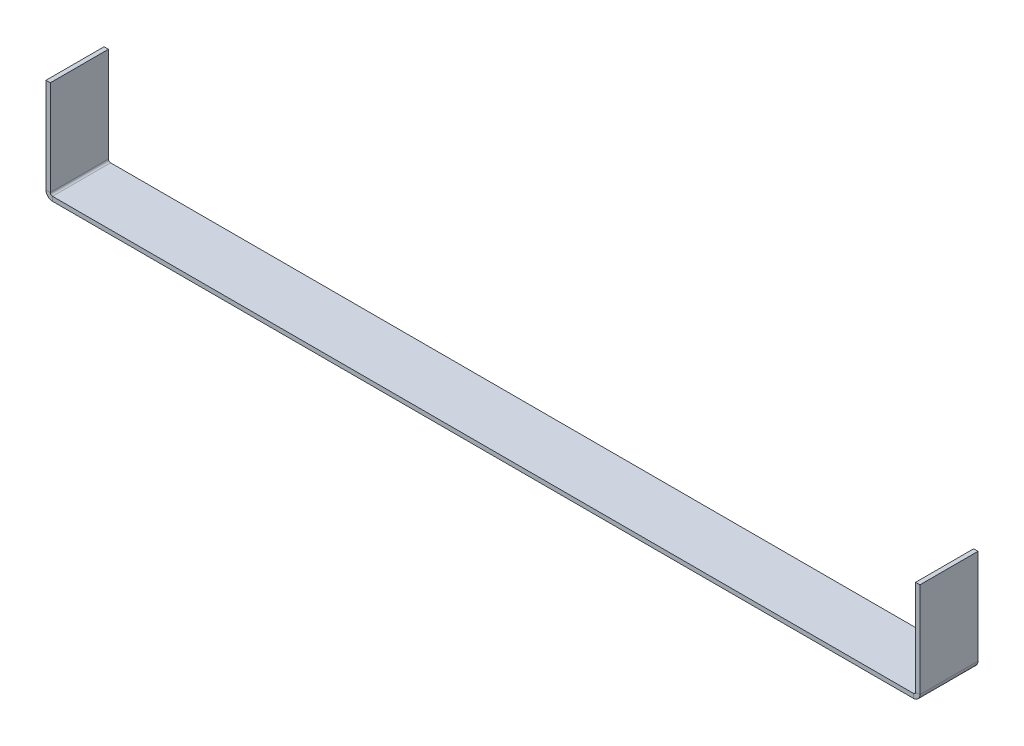
SolidWorks part; units mm, degrees
note: The reader was unsure of these and kept them because the rebuilt part matched: flange length of "Ребро-кромка1", "Ребро-кромка2".
ref_plane "Спереди" through (0, 0, 0) normal (0, 0, 1) x (1, 0, 0)
ref_plane "Сверху" through (0, 0, 0) normal (0, 1, 0) x (1, 0, 0)
ref_plane "Справа" through (0, 0, 0) normal (1, 0, 0) x (0, 0, -1)
sketch "Эскиз1" plane through (0, 0, 0) normal (0, 1, 0) x (1, 0, 0)
  line L1 (0, 0) -> (301, 0)
  line L2 (0, 0) -> (0, 20)
  line L3 (0, 20) -> (301, 20)
  line L4 (301, 0) -> (301, 20)
base flange "Базовая кромка1" sketch "Эскиз1" thickness 1.5 reverse thickness direction no parameters "D1"=0.7366
edge flange "Ребро-кромка1" sketch "Эскиз8" flange angle 90 flange length 35 flange position material inside bend radius 0.7366 thickness 1.5 relief rectangular parameters "D6"=10
sketch "Эскиз8" plane through (0, 0, 0) normal (-1, 0, 0) x (0, 0, 1)
  line L0 (-20, 0) -> (0, 0) construction
  line L1 (-20, 0) -> (0, 0)
  line L2 (-20, 0) -> (-20, 33.5)
  line L3 (-20, 33.5) -> (0, 33.5)
  line L4 (0, 33.5) -> (0, 0)
bend "EdgeBend1" bend radius 0.7366 bend angle 90 parameters "D5"=1
edge flange "Ребро-кромка2" sketch "Эскиз11" flange angle 90 flange length 35 flange position material inside bend radius 0.7366 thickness 1.5 relief rectangular parameters "D6"=10
sketch "Эскиз11" plane through (301, 0, 0) normal (1, 0, 0) x (0, 0, -1)
  line L2 (0, 0) -> (0, 33.5)
  line L3 (0, 33.5) -> (20, 33.5)
  line L4 (20, 33.5) -> (20, 0)
  line L7 (0, 0) -> (20, 0) construction
  line L8 (0, 0) -> (20, 0)
bend "EdgeBend2" bend radius 0.7366 bend angle 90 parameters "D5"=2
sketch "Сгиб-Линии1" [suppressed] plane through (0, 0, 0) normal (0, 1, 0) x (1, 0, 0)
sketch "Граничная рамка1" [suppressed] plane through (0, 0, 0) normal (0, 1, 0) x (1, 0, 0)
sheet metal parameters "Листовой металл1" thickness 1.5 parameters "D1"=0.7366
flat pattern "Развертка1" [suppressed]
sketch "Сгиб-Линии2" plane through (0, 0, 0) normal (0, 1, 0) x (1, 0, 0)
sketch3d "Граничная рамка2" [suppressed]
  line L0 (-200, 20, 0) -> (0, 20, 0) construction
  line L1 (-200, 0, 0) -> (0, 0, 0) construction
  line L2 (-200, 20, 0) -> (-200, 0, 0) construction
  line L3 (0, 20, 0) -> (0, 0, 0) construction
sheet metal parameters "Листовой металл2" thickness 1.5 parameters "D1"=0.7366
flat pattern "Развертка1"
sketch "Сгиб-Линии2" plane through (0, 0, 0) normal (0, 1, 0) x (1, 0, 0)
  line L0 (1.069, 20) -> (1.069, 0) construction
  line L1 (1.069, 20) -> (1.069, 0) construction
sketch3d "Граничная рамка2" [suppressed]
  line L0 (200, 20, 0) -> (-30.5985, 20, 0) construction
  line L1 (200, 0, 0) -> (-30.5985, 0, 0) construction
  line L2 (200, 20, 0) -> (200, 0, 0) construction
  line L3 (-30.5985, 20, 0) -> (-30.5985, 0, 0) construction
bend of the flat pattern "Плоское состояние-<EdgeBend1>1"
sheet metal parameters "Листовой металл3" thickness 1.5 parameters "D1"=0.7366
flat pattern "Развертка1"
sketch "Сгиб-Линии2" plane through (0, 0, 0) normal (0, 1, 0) x (1, 0, 0)
  line L0 (1.069, 20) -> (1.069, 0) construction
  line L1 (1.069, 20) -> (1.069, 0) construction
  line L2 (299.931, 0) -> (299.931, 20) construction
  line L3 (299.931, 0) -> (299.931, 20) construction
sketch3d "Граничная рамка2" [suppressed]
  line L0 (333.8619, 20, 0) -> (-32.8619, 20, 0) construction
  line L1 (333.8619, 0, 0) -> (-32.8619, 0, 0) construction
  line L2 (333.8619, 20, 0) -> (333.8619, 0, 0) construction
  line L3 (-32.8619, 20, 0) -> (-32.8619, 0, 0) construction
bend of the flat pattern "Плоское состояние-<EdgeBend1>1"
bend of the flat pattern "Плоское состояние-<EdgeBend2>1"
